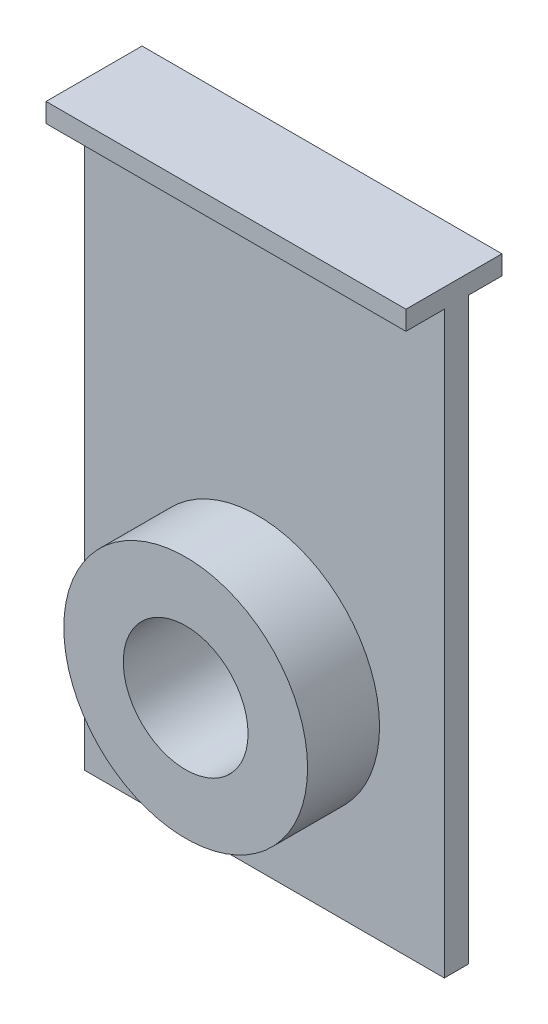
SolidWorks part; units mm, degrees
ref_plane "Front Plane" through (0, 0, 0) normal (0, 0, 1) x (1, 0, 0)
ref_plane "Top Plane" through (0, 0, 0) normal (0, 1, 0) x (1, 0, 0)
ref_plane "Right Plane" through (0, 0, 0) normal (1, 0, 0) x (0, 0, -1)
sketch "Sketch12" plane through (0, 0, 0) normal (0, 0, 1) x (1, 0, 0)
  line L0 (62.1258, 0) -> (62.1258, 124.71)
  line L1 (62.1258, 124.71) -> (137.1258, 124.71)
  line L2 (62.1258, 0) -> (137.1258, 0)
  line L3 (137.1258, 124.71) -> (137.1258, 0)
  circle A0 centre (99.6258, 37.5) radius 25.4
  circle A1 centre (99.6258, 37.5) radius 6.5
  dimension "D3" = 50.8
  dimension "D4" = 13
  dimension "D1" = 124.71
  dimension "D2" = 75
extrude "Boss-Extrude10" add sketch "Sketch12" along normal blind 5 separate body contours L1 L3 L2 L0
sketch "Sketch15" plane through (0, 0, 5) normal (0, 0, 1) x (1, 0, 0)
  circle A0 centre (98.2196, 38.6276) radius 25.4
  dimension "D1" = 50.8
extrude "Boss-Extrude11" add sketch "Sketch15" along normal blind 15
sketch "Sketch23" plane through (0, 0, 20) normal (0, 0, 1) x (1, 0, 0)
  circle A0 centre (98.2196, 38.6276) radius 13
  dimension "D1" = 26
extrude "Cut-Extrude7" cut sketch "Sketch23" against normal through all
sketch "Sketch24" plane through (0, 0, 5) normal (0, 0, 1) x (1, 0, 0)
  line L0 (62.1258, 124.71) -> (62.1258, 120.71)
  line L1 (62.1258, 0) -> (62.1258, 124.71) construction
  line L2 (62.1258, 120.71) -> (137.1258, 120.71)
  line L3 (137.1258, 124.71) -> (137.1258, 0) construction
  line L4 (137.1258, 120.71) -> (137.1258, 124.71)
  line L5 (137.1258, 124.71) -> (62.1258, 124.71)
  dimension "D1" = 4
extrude "Boss-Extrude13" add sketch "Sketch24" along normal blind 8 and the other way blind 12
